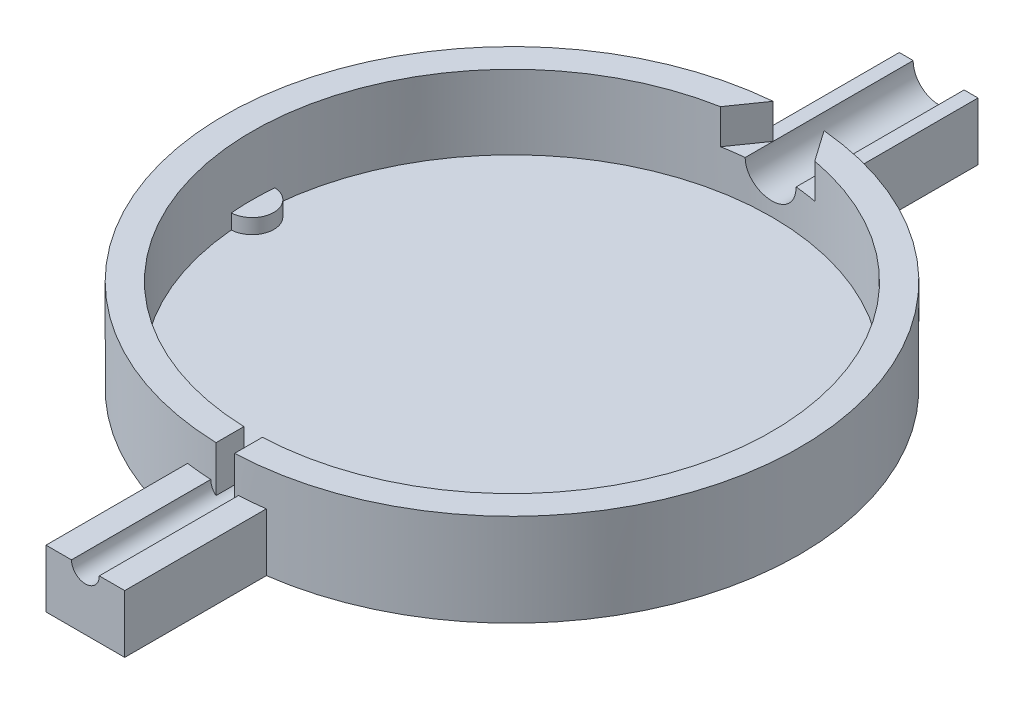
SolidWorks part; units mm, degrees
ref_plane "Front Plane" through (0, 0, 0) normal (0, 0, 1) x (1, 0, 0)
ref_plane "Top Plane" through (0, 0, 0) normal (0, 1, 0) x (1, 0, 0)
ref_plane "Right Plane" through (0, 0, 0) normal (1, 0, 0) x (0, 0, -1)
sketch "Sketch1" plane through (0, 0, 0) normal (0, 1, 0) x (1, 0, 0)
  circle A0 centre (0, 0) radius 31.06
  dimension "D1" = 62.12
extrude "Boss-Extrude1" add sketch "Sketch1" along normal blind 10
sketch "Sketch2" plane through (0, 10, 0) normal (0, 1, 0) x (1, 0, 0)
  circle A0 centre (0, 0) radius 28.06
  circle A1 centre (0, 0) radius 31.06 construction
  circle A2 centre (0, 0) radius 31.06
  dimension "D1" = 3
extrude "Cut-Extrude1" cut sketch "Sketch2" against normal blind 8 contours A0 region at (0, 10, 0)
sketch "Sketch3" plane through (0, 2, 0) normal (0, 1, 0) x (1, 0, 0)
  arc A0 (-27.9616, -2.3479) -> (-27.9616, 2.3479) centre (-28.06, 0) ccw
  circle A1 centre (0, 0) radius 28.06 construction
  arc A2 (27.9616, 2.3479) -> (27.9616, -2.3479) centre (28.06, 0) ccw
  arc A3 (27.9616, -2.3479) -> (27.9616, 2.3479) centre (0, 0) ccw
  arc A4 (-27.9616, 2.3479) -> (-27.9616, -2.3479) centre (0, 0) ccw
  dimension "D1" = 4.7
  dimension "D2" = 4.7
extrude "Boss-Extrude2" add sketch "Sketch3" along normal blind 1.6
sketch "Sketch4" plane through (0, 0, 0) normal (0, 0, 1) x (1, 0, 0)
  line L0 (27.9616, 2) -> (-27.9616, 2) construction
  line L1 (27.9616, 2) -> (-27.9616, 2)
  line L2 (0, 0) -> (0, 4.7714)
  line L3 (28.06, 10) -> (-28.06, 10) construction
  line L4 (28.06, 10) -> (-28.06, 10)
  line L5 (-2.75, 6.25) -> (-2.75, 10)
  line L6 (2.75, 6.25) -> (2.75, 10)
  circle A0 centre (0, 6.25) radius 2.75
  dimension "D1" = 5.5
  dimension "D2" = 4.25
extrude "Cut-Extrude2" cut sketch "Sketch4" against normal through all contours A0 L6 L4 L5 | A0 region at (0, 9.0865, 0)
sketch "Sketch5" plane through (0, 0, 0) normal (0, 0, 1) x (1, 0, 0)
  line L0 (28.06, 10) -> (-28.06, 10) construction
  line L1 (1.0982, 3.999) -> (-0.9018, 3.999)
  line L2 (1.0982, 3.999) -> (1.0982, 10)
  line L3 (1.0982, 5.999) -> (-0.9018, 5.999)
  line L4 (-0.9018, 3.999) -> (-0.9018, 10)
  line L5 (1.0982, 3.999) -> (-0.9018, 5.999) construction
  line L6 (1.0982, 5.999) -> (-0.9018, 3.999) construction
  line L7 (1.0982, 10) -> (-0.9018, 10)
  point P0 (0.0982, 4.999)
  dimension "D1" = 2
  dimension "D2" = 2
  dimension "D3" = 5
extrude "Cut-Extrude3" cut sketch "Sketch5" along normal through all contours L2 L7 L4 L1
ref_plane "Plane1" through (0, 0, -28.06) normal (0, 0, 1) x (1, 0, 0)
sketch "Sketch6" plane through (0, 0, -28.06) normal (0, 0, 1) x (1, 0, 0)
  line L0 (-31.06, 0) -> (31.06, 0) construction
  line L1 (-4.25, 0) -> (4.25, 0)
  line L2 (4.25, 6.25) -> (4.25, 0)
  line L3 (-4.25, 6.25) -> (-4.25, 0)
  line L4 (-4.25, 6.25) -> (-2.75, 6.25)
  line L5 (-2.75, 6.25) -> (-2.7454, 6.232)
  line L6 (2.75, 6.25) -> (4.25, 6.25)
  arc A0 (-2.75, 6.25) -> (2.75, 6.25) centre (0, 6.25) ccw construction
  arc A1 (-2.75, 6.25) -> (2.75, 6.25) centre (0, 6.25) ccw
extrude "Boss-Extrude3" add sketch "Sketch6" against normal blind 18 contours A1 L6 L2 L1 L3 L4
ref_plane "Plane2" through (0, 0, 28.06) normal (0, 0, -1) x (-1, 0, 0)
sketch "Sketch7" plane through (0, 0, 28.06) normal (0, 0, -1) x (-1, 0, 0)
  line L5 (4.25, 6.25) -> (2.75, 6.25)
  line L6 (-2.75, 6.25) -> (-4.25, 6.25)
  line L7 (-4.25, 6.25) -> (-4.25, 0)
  line L8 (-4.25, 0) -> (4.25, 0)
  line L9 (4.25, 0) -> (4.25, 6.25)
  line L10 (4.25, 6.25) -> (1.5, 6.25)
  line L11 (-1.5, 6.25) -> (-4.25, 6.25)
  line L12 (-4.25, 6.25) -> (-4.25, 0)
  line L13 (-4.25, 0) -> (4.25, 0)
  line L14 (4.25, 0) -> (4.25, 6.25)
  arc A0 (-1.5, 6.25) -> (1.5, 6.25) centre (0, 6.25) ccw
  arc A1 (-2.75, 6.25) -> (2.75, 6.25) centre (0, 6.25) ccw
  dimension "D2" = 3
  dimension "D1" = 0
extrude "Boss-Extrude4" add sketch "Sketch7" against normal blind 18
sketch "Sketch8" plane through (0, 10, 0) normal (0, 1, 0) x (1, 0, 0)
  line L0 (2.75, 27.9249) -> (2.75, 30.938) construction
  line L1 (-2.75, 27.9249) -> (-2.75, 30.938) construction
  line L2 (2.75, 27.9249) -> (2.75, 30.938)
  line L3 (-2.75, 27.9249) -> (-2.75, 30.938)
  line L4 (-2.75, 30.938) -> (-5.0913, 27.5942)
  line L5 (2.75, 30.938) -> (5.0913, 27.5942)
  arc A0 (-2.75, 27.9249) -> (-0.9018, -28.0455) centre (0, 0) ccw construction
  arc A1 (1.0982, -28.0385) -> (2.75, 27.9249) centre (0, 0) ccw construction
  arc A2 (-2.75, 27.9249) -> (-5.0913, 27.5942) centre (0, 0) ccw
  arc A3 (5.0913, 27.5942) -> (2.75, 27.9249) centre (0, 0) ccw
  dimension "D1" = 35
  dimension "D2" = 35
extrude "Cut-Extrude4" cut sketch "Sketch8" against normal up to surface (3.75 mm away) up to face at (3.5003, 6.25, -38.4587)
